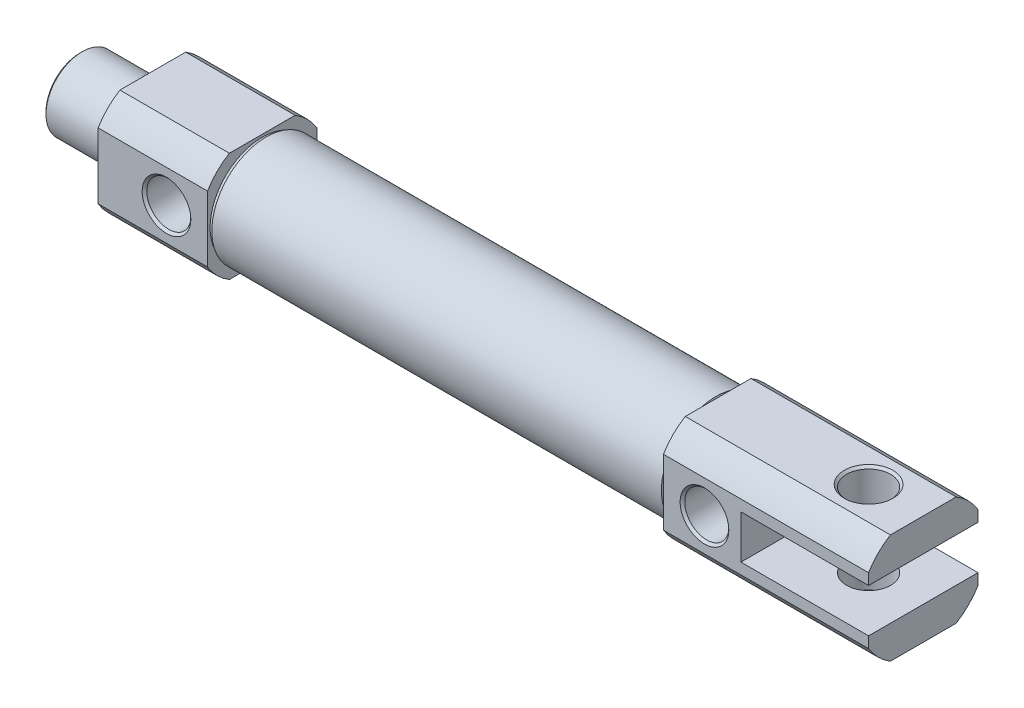
SolidWorks part; units mm, degrees
ref_plane "Front Plane" through (0, 0, 0) normal (0, 0, 1) x (1, 0, 0)
ref_plane "Top Plane" through (0, 0, 0) normal (0, 1, 0) x (1, 0, 0)
ref_plane "Right Plane" through (0, 0, 0) normal (1, 0, 0) x (0, 0, -1)
sketch "Sketch1" plane through (0, 0, 0) normal (1, 0, 0) x (0, 0, -1)
  circle A0 centre (0, 0) radius 5
  circle A1 centre (0, 0) radius 5.97
  dimension "D1" = 10
  dimension "D2" = 11.94
extrude "Boss-Extrude1" add sketch "Sketch1" along normal mid plane 30.4 contours A0 region at (0, 0, 0)
extrude "Boss-Extrude2" add sketch "Sketch1<3>" along normal mid plane 50
sketch "Sketch1<3>" plane through (0, 0, 0) normal (1, 0, 0) x (0, 0, -1) same geometry as "Sketch1"
chamfer "Chamfer1" distance 0.254 angle 60 1 edges at (25, 0, -5.97) first distance on face at (25, 0, -5.97)
chamfer "Chamfer2" distance 0.254 angle 60 1 edges at (-25, 0, -5.97) first distance on face at (-25, 0, -5.97)
sketch "Sketch2" plane through (25, 0, 0) normal (1, 0, 0) x (0, 0, -1)
  line L1 (6, -6) -> (-6, -6)
  line L2 (6, -6) -> (6, 6)
  line L3 (6, 6) -> (-6, 6)
  line L4 (-6, -6) -> (-6, 6)
  line L5 (6, -6) -> (-6, 6) construction
  line L6 (6, 6) -> (-6, -6) construction
  circle A0 centre (0, 0) radius 7
  point P0 (0, 0)
  dimension "D3" = 14
  dimension "D1" = 12
  dimension "D2" = 12
sketch "Sketch3" plane through (25, 0, 0) normal (1, 0, 0) x (0, 0, -1)
  line L0 (-6, 3.6055) -> (-6, -3.6055)
  line L1 (6, 3.6055) -> (6, -3.6055)
  line L2 (-3.6055, 6) -> (3.6055, 6)
  line L3 (-3.6055, -6) -> (3.6055, -6)
  line L4 (6, -6) -> (6, 6) construction
  line L5 (6, 6) -> (-6, 6) construction
  line L6 (-6, -6) -> (-6, 6) construction
  line L7 (6, -6) -> (-6, -6) construction
  arc A0 (-6, 3.6055) -> (-3.6055, 6) centre (0, 0) cw
  arc A1 (6, 3.6055) -> (3.6055, 6) centre (0, 0) ccw
  arc A2 (6, -3.6055) -> (3.6055, -6) centre (0, 0) cw
  arc A3 (-6, -3.6055) -> (-3.6055, -6) centre (0, 0) ccw
  circle A4 centre (0, 0) radius 7 construction
extrude "Boss-Extrude3" add sketch "Sketch3" along normal blind 22.5
sketch "Sketch5" plane through (0, 6, 0) normal (0, 1, 0) x (1, 0, 0)
  line L0 (47.5, 3.6055) -> (47.5, -3.6055) construction
  circle A0 centre (41.5, 0) radius 2.415
  dimension "D2" = 4.8301
  dimension "D1" = 6
extrude "Cut-Extrude2" cut sketch "Sketch5" against normal through all
sketch "Sketch6" plane through (0, 0, 6) normal (0, 0, 1) x (1, 0, 0)
  line L0 (47.5, 3.6055) -> (47.5, -3.6055) construction
  line L1 (33.5, -2.39) -> (47.5, -2.39)
  line L2 (33.5, -2.39) -> (33.5, 2.39)
  line L3 (33.5, 2.39) -> (47.5, 2.39)
  line L4 (47.5, -2.39) -> (47.5, 2.39)
  line L5 (33.5, -2.39) -> (47.5, 2.39) construction
  line L6 (33.5, 2.39) -> (47.5, -2.39) construction
  point P0 (40.5, 0)
  dimension "D1" = 14
  dimension "D2" = 4.78
extrude "Cut-Extrude3" cut sketch "Sketch6" against normal through all
extrude "Boss-Extrude4" add sketch "Sketch3<2>" against normal blind 12 from surface starting at face at (-25, 0, -5.716)
sketch "Sketch3<2>" plane through (25, 0, 0) normal (1, 0, 0) x (0, 0, -1) same geometry as "Sketch3"
sketch "Sketch4" plane through (0, 0, 6) normal (0, 0, 1) x (1, 0, 0)
  line L0 (25, 3.6055) -> (25, -3.6055) construction
  line L1 (-25, 3.6055) -> (-25, -3.6055) construction
  circle A0 centre (29.5001, 0) radius 2.415
  circle A1 centre (-29.5001, 0) radius 2.415
  dimension "D2" = 4.8301
  dimension "D1" = 4.5001
  dimension "D3" = 4.5001
extrude "Cut-Extrude4" cut sketch "Sketch4" against normal blind 6
sketch "Sketch8" plane through (-37, 0, 0) normal (-1, 0, 0) x (0, 0, 1)
  circle A0 centre (0, 0) radius 3.9688
  circle A1 centre (0, 0) radius 2.1827
  dimension "D1" = 4.3655
  dimension "D2" = 7.9375
extrude "Boss-Extrude5" add sketch "Sketch8" along normal blind 8
chamfer "Chamfer5" distance 0.254 angle 45 6 edges at (41.5, -6, 2.415) (41.5, 6, 2.415) (31.9152, 0, 6) (-27.0851, 0, 6) (-45, 0, 3.9688) (-45, 0, 2.1827)
equation "\"D2@Sketch2\"=\"D1@Sketch2\""
